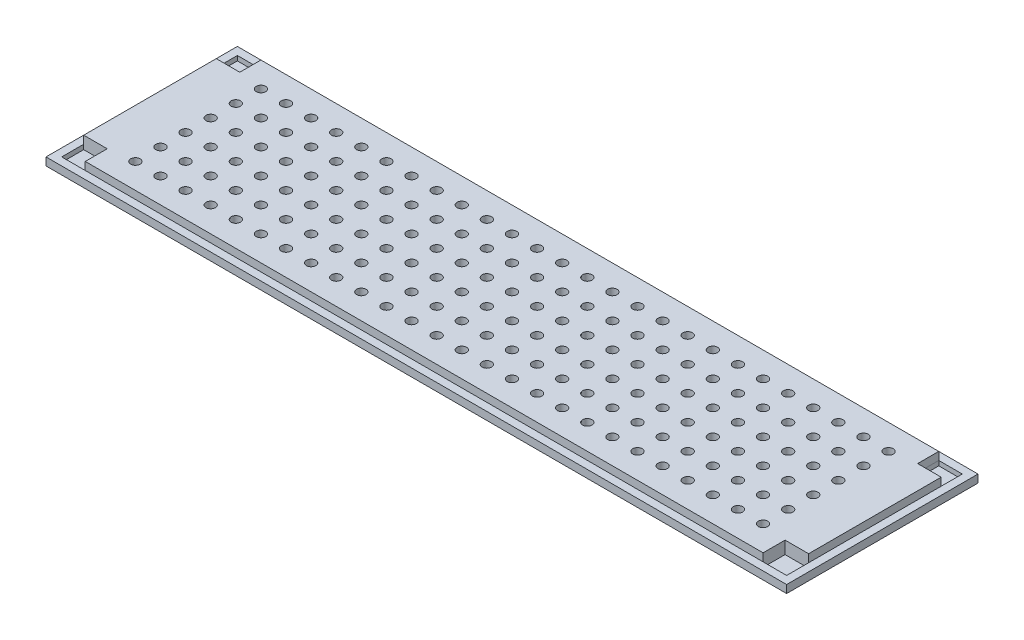
SolidWorks part; units mm, degrees
ref_plane "Front Plane" through (0, 0, 0) normal (0, 0, 1) x (1, 0, 0)
ref_plane "Top Plane" through (0, 0, 0) normal (0, 1, 0) x (1, 0, 0)
ref_plane "Right Plane" through (0, 0, 0) normal (1, 0, 0) x (0, 0, -1)
sketch "Sketch1" plane through (0, 0, 0) normal (0, 1, 0) x (1, 0, 0)
  line L5 (-118, 30.49) -> (118, 30.49)
  line L6 (-118, 30.49) -> (-118, -30.49)
  line L7 (-118, -30.49) -> (118, -30.49)
  line L8 (118, 30.49) -> (118, -30.49)
  line L9 (-118, 30.49) -> (118, -30.49) construction
  line L10 (-118, -30.49) -> (118, 30.49) construction
  point P0 (0, 0)
  point P1 (0, 0)
  dimension "D1" = 236
  dimension "D2" = 60.98
extrude "Boss-Extrude2" add sketch "Sketch1" along normal blind 2.5
sketch "Sketch2" plane through (0, 2.5, 0) normal (0, 1, 0) x (1, 0, 0)
  line L0 (-107.9977, 27.99) -> (-107.9977, 21.2567)
  line L7 (-107.9977, 21.2567) -> (-115.5, 21.2567)
  line L8 (-115.5, -20.9859) -> (-115.5, 21.2567) construction
  line L9 (-115.5, 21.2567) -> (-115.5, -20.9859)
  line L10 (-115.5, -20.9859) -> (-107.9977, -20.9859)
  line L11 (-107.9977, -20.9859) -> (-107.9977, -27.9859)
  line L12 (-107.9977, -27.9859) -> (107.9977, -27.9859)
  line L13 (107.9977, -27.9859) -> (107.9977, -20.9859)
  line L14 (107.9977, -20.9859) -> (115.5, -20.9859)
  line L15 (115.5, -20.9859) -> (115.5, 21.2567)
  line L16 (115.5, 21.2567) -> (108, 21.2581)
  line L17 (108, 21.2581) -> (107.9977, 27.99)
  line L18 (107.9977, 27.99) -> (-107.9977, 27.99)
  point P0 (0, 0)
  dimension "D1" = 215.9954
extrude "Boss-Extrude3" add sketch "Sketch2" along normal blind 2.5
sketch "Sketch4" plane through (0, 2.5, 0) normal (0, 1, 0) x (1, 0, 0)
  line L0 (-107.9977, 27.99) -> (-115.5, 27.99)
  line L1 (-115.5, 21.2567) -> (-115.5, 27.99)
  line L2 (-107.9977, 21.2567) -> (-115.5, 21.2567) construction
  line L3 (-115.5, 21.2567) -> (-115.5, -20.9859) construction
  line L4 (-115.5, 21.2567) -> (-107.9977, 21.2567)
  line L5 (-107.9977, 21.2567) -> (-107.9977, 27.99)
  line L6 (0, -2.75) -> (0, 2.75) construction
  line L9 (-107.9977, -21.2567) -> (-107.9977, -27.99)
  line L10 (-107.9977, -27.99) -> (-115.5, -27.99)
  line L11 (-115.5, -21.2567) -> (-115.5, -27.99)
  line L12 (-115.5, -21.2567) -> (-115.5, -20.9859)
  line L13 (-115.5, -20.9859) -> (-107.9977, -20.9859)
  line L14 (-115.5, -20.9859) -> (-107.9977, -20.9859) construction
  line L15 (-115.5, -20.9859) -> (-107.9977, -20.9859) construction
  line L16 (-107.9977, -20.9859) -> (-107.9977, -21.2567)
  line L17 (115.5, -21.2567) -> (115.5, -20.9859)
  line L18 (115.5, -20.9859) -> (107.9977, -20.9859)
  line L19 (107.9977, -20.9859) -> (107.9977, -21.2567)
  line L20 (107.9977, -21.2567) -> (107.9977, -27.99)
  line L21 (107.9977, -27.99) -> (115.5, -27.99)
  line L22 (115.5, -21.2567) -> (115.5, -27.99)
  line L23 (115.5, 21.2567) -> (107.9977, 21.2567)
  line L24 (107.9977, 21.2567) -> (107.9977, 27.99)
  line L25 (107.9977, 27.99) -> (115.5, 27.99)
  line L26 (115.5, 21.2567) -> (115.5, 27.99)
extrude "Cut-Extrude2" cut sketch "Sketch4" against normal blind 1.5
sketch "Sketch5" plane through (0, 5, 0) normal (0, 1, 0) x (1, 0, 0)
  line L0 (107.9977, 27.99) -> (-107.9977, 27.99) construction
  line L1 (-107.9977, 21.2567) -> (-107.9977, 27.99) construction
  circle A0 centre (-99.9977, 19.99) radius 1.5
  circle A1 centre (-91.9977, 19.99) radius 1.5
  circle A2 centre (-83.9977, 19.99) radius 1.5
  circle A3 centre (-75.9977, 19.99) radius 1.5
  circle A4 centre (-67.9977, 19.99) radius 1.5
  circle A5 centre (-59.9977, 19.99) radius 1.5
  circle A6 centre (-51.9977, 19.99) radius 1.5
  circle A7 centre (-43.9977, 19.99) radius 1.5
  circle A8 centre (-35.9977, 19.99) radius 1.5
  circle A9 centre (-27.9977, 19.99) radius 1.5
  circle A10 centre (-19.9977, 19.99) radius 1.5
  circle A11 centre (-11.9977, 19.99) radius 1.5
  circle A12 centre (-3.9977, 19.99) radius 1.5
  circle A13 centre (4.0023, 19.99) radius 1.5
  circle A14 centre (12.0023, 19.99) radius 1.5
  circle A15 centre (20.0023, 19.99) radius 1.5
  circle A16 centre (28.0023, 19.99) radius 1.5
  circle A17 centre (36.0023, 19.99) radius 1.5
  circle A18 centre (44.0023, 19.99) radius 1.5
  circle A19 centre (52.0023, 19.99) radius 1.5
  circle A20 centre (60.0023, 19.99) radius 1.5
  circle A21 centre (68.0023, 19.99) radius 1.5
  circle A22 centre (76.0023, 19.99) radius 1.5
  circle A23 centre (84.0023, 19.99) radius 1.5
  circle A24 centre (92.0023, 19.99) radius 1.5
  circle A25 centre (100.0023, 19.99) radius 1.5
  circle A26 centre (-91.9977, 11.99) radius 1.5
  circle A27 centre (-83.9977, 11.99) radius 1.5
  circle A28 centre (-75.9977, 11.99) radius 1.5
  circle A29 centre (-67.9977, 11.99) radius 1.5
  circle A30 centre (-59.9977, 11.99) radius 1.5
  circle A31 centre (-51.9977, 11.99) radius 1.5
  circle A32 centre (-43.9977, 11.99) radius 1.5
  circle A33 centre (-35.9977, 11.99) radius 1.5
  circle A34 centre (-27.9977, 11.99) radius 1.5
  circle A35 centre (-19.9977, 11.99) radius 1.5
  circle A36 centre (-11.9977, 11.99) radius 1.5
  circle A37 centre (-3.9977, 11.99) radius 1.5
  circle A38 centre (4.0023, 11.99) radius 1.5
  circle A39 centre (12.0023, 11.99) radius 1.5
  circle A40 centre (20.0023, 11.99) radius 1.5
  circle A41 centre (28.0023, 11.99) radius 1.5
  circle A42 centre (36.0023, 11.99) radius 1.5
  circle A43 centre (44.0023, 11.99) radius 1.5
  circle A44 centre (52.0023, 11.99) radius 1.5
  circle A45 centre (60.0023, 11.99) radius 1.5
  circle A46 centre (68.0023, 11.99) radius 1.5
  circle A47 centre (76.0023, 11.99) radius 1.5
  circle A48 centre (84.0023, 11.99) radius 1.5
  circle A49 centre (92.0023, 11.99) radius 1.5
  circle A50 centre (100.0023, 11.99) radius 1.5
  circle A51 centre (-91.9977, 3.99) radius 1.5
  circle A52 centre (-83.9977, 3.99) radius 1.5
  circle A53 centre (-75.9977, 3.99) radius 1.5
  circle A54 centre (-67.9977, 3.99) radius 1.5
  circle A55 centre (-59.9977, 3.99) radius 1.5
  circle A56 centre (-51.9977, 3.99) radius 1.5
  circle A57 centre (-43.9977, 3.99) radius 1.5
  circle A58 centre (-35.9977, 3.99) radius 1.5
  circle A59 centre (-27.9977, 3.99) radius 1.5
  circle A60 centre (-19.9977, 3.99) radius 1.5
  circle A61 centre (-11.9977, 3.99) radius 1.5
  circle A62 centre (-3.9977, 3.99) radius 1.5
  circle A63 centre (4.0023, 3.99) radius 1.5
  circle A64 centre (12.0023, 3.99) radius 1.5
  circle A65 centre (20.0023, 3.99) radius 1.5
  circle A66 centre (28.0023, 3.99) radius 1.5
  circle A67 centre (36.0023, 3.99) radius 1.5
  circle A68 centre (44.0023, 3.99) radius 1.5
  circle A69 centre (52.0023, 3.99) radius 1.5
  circle A70 centre (60.0023, 3.99) radius 1.5
  circle A71 centre (68.0023, 3.99) radius 1.5
  circle A72 centre (76.0023, 3.99) radius 1.5
  circle A73 centre (84.0023, 3.99) radius 1.5
  circle A74 centre (92.0023, 3.99) radius 1.5
  circle A75 centre (100.0023, 3.99) radius 1.5
  circle A76 centre (-91.9977, -4.01) radius 1.5
  circle A77 centre (-83.9977, -4.01) radius 1.5
  circle A78 centre (-75.9977, -4.01) radius 1.5
  circle A79 centre (-67.9977, -4.01) radius 1.5
  circle A80 centre (-59.9977, -4.01) radius 1.5
  circle A81 centre (-51.9977, -4.01) radius 1.5
  circle A82 centre (-43.9977, -4.01) radius 1.5
  circle A83 centre (-35.9977, -4.01) radius 1.5
  circle A84 centre (-27.9977, -4.01) radius 1.5
  circle A85 centre (-19.9977, -4.01) radius 1.5
  circle A86 centre (-11.9977, -4.01) radius 1.5
  circle A87 centre (-3.9977, -4.01) radius 1.5
  circle A88 centre (4.0023, -4.01) radius 1.5
  circle A89 centre (12.0023, -4.01) radius 1.5
  circle A90 centre (20.0023, -4.01) radius 1.5
  circle A91 centre (28.0023, -4.01) radius 1.5
  circle A92 centre (36.0023, -4.01) radius 1.5
  circle A93 centre (44.0023, -4.01) radius 1.5
  circle A94 centre (52.0023, -4.01) radius 1.5
  circle A95 centre (60.0023, -4.01) radius 1.5
  circle A96 centre (68.0023, -4.01) radius 1.5
  circle A97 centre (76.0023, -4.01) radius 1.5
  circle A98 centre (84.0023, -4.01) radius 1.5
  circle A99 centre (92.0023, -4.01) radius 1.5
  circle A100 centre (100.0023, -4.01) radius 1.5
  circle A101 centre (-91.9977, -12.01) radius 1.5
  circle A102 centre (-83.9977, -12.01) radius 1.5
  circle A103 centre (-75.9977, -12.01) radius 1.5
  circle A104 centre (-67.9977, -12.01) radius 1.5
  circle A105 centre (-59.9977, -12.01) radius 1.5
  circle A106 centre (-51.9977, -12.01) radius 1.5
  circle A107 centre (-43.9977, -12.01) radius 1.5
  circle A108 centre (-35.9977, -12.01) radius 1.5
  circle A109 centre (-27.9977, -12.01) radius 1.5
  circle A110 centre (-19.9977, -12.01) radius 1.5
  circle A111 centre (-11.9977, -12.01) radius 1.5
  circle A112 centre (-3.9977, -12.01) radius 1.5
  circle A113 centre (4.0023, -12.01) radius 1.5
  circle A114 centre (12.0023, -12.01) radius 1.5
  circle A115 centre (20.0023, -12.01) radius 1.5
  circle A116 centre (28.0023, -12.01) radius 1.5
  circle A117 centre (36.0023, -12.01) radius 1.5
  circle A118 centre (44.0023, -12.01) radius 1.5
  circle A119 centre (52.0023, -12.01) radius 1.5
  circle A120 centre (60.0023, -12.01) radius 1.5
  circle A121 centre (68.0023, -12.01) radius 1.5
  circle A122 centre (76.0023, -12.01) radius 1.5
  circle A123 centre (84.0023, -12.01) radius 1.5
  circle A124 centre (92.0023, -12.01) radius 1.5
  circle A125 centre (100.0023, -12.01) radius 1.5
  circle A126 centre (-91.9977, -20.01) radius 1.5
  circle A127 centre (-83.9977, -20.01) radius 1.5
  circle A128 centre (-75.9977, -20.01) radius 1.5
  circle A129 centre (-67.9977, -20.01) radius 1.5
  circle A130 centre (-59.9977, -20.01) radius 1.5
  circle A131 centre (-51.9977, -20.01) radius 1.5
  circle A132 centre (-43.9977, -20.01) radius 1.5
  circle A133 centre (-35.9977, -20.01) radius 1.5
  circle A134 centre (-27.9977, -20.01) radius 1.5
  circle A135 centre (-19.9977, -20.01) radius 1.5
  circle A136 centre (-11.9977, -20.01) radius 1.5
  circle A137 centre (-3.9977, -20.01) radius 1.5
  circle A138 centre (4.0023, -20.01) radius 1.5
  circle A139 centre (12.0023, -20.01) radius 1.5
  circle A140 centre (20.0023, -20.01) radius 1.5
  circle A141 centre (28.0023, -20.01) radius 1.5
  circle A142 centre (36.0023, -20.01) radius 1.5
  circle A143 centre (44.0023, -20.01) radius 1.5
  circle A144 centre (52.0023, -20.01) radius 1.5
  circle A145 centre (60.0023, -20.01) radius 1.5
  circle A146 centre (68.0023, -20.01) radius 1.5
  circle A147 centre (76.0023, -20.01) radius 1.5
  circle A148 centre (84.0023, -20.01) radius 1.5
  circle A149 centre (92.0023, -20.01) radius 1.5
  circle A150 centre (100.0023, -20.01) radius 1.5
  circle A151 centre (-99.9977, 11.99) radius 1.5
  circle A152 centre (-99.9977, 3.99) radius 1.5
  circle A153 centre (-99.9977, -4.01) radius 1.5
  circle A154 centre (-99.9977, -12.01) radius 1.5
  circle A155 centre (-99.9977, -20.01) radius 1.5
  dimension "D1" = 3
  dimension "D2" = 8
  dimension "D3" = 8
  dimension "D4" = 26
  dimension "D5" = 6
extrude "Cut-Extrude3" cut sketch "Sketch5" against normal blind 10
